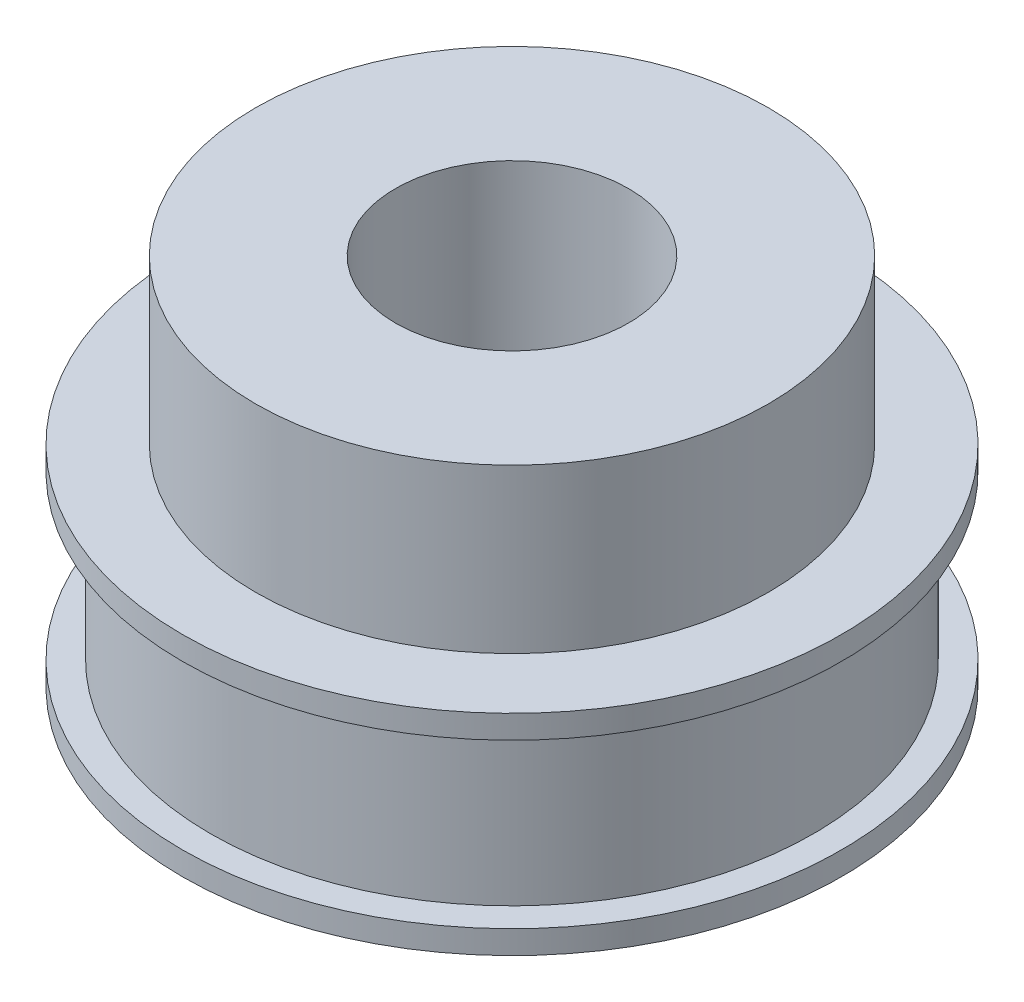
SolidWorks part; units mm, degrees
ref_plane "前视基准面" through (0, 0, 0) normal (0, 0, 1) x (1, 0, 0)
ref_plane "上视基准面" through (0, 0, 0) normal (0, 1, 0) x (1, 0, 0)
ref_plane "右视基准面" through (0, 0, 0) normal (1, 0, 0) x (0, 0, -1)
sketch "草图1" plane through (0, 0, 0) normal (0, 1, 0) x (1, 0, 0)
  circle A0 centre (0, 0) radius 12.935
  dimension "D1" = 25.87
extrude "凸台-拉伸1" add sketch "草图1" along normal blind 7
ref_plane "基准面1" through (0, 3.5, 0) normal (0, 1, 0) x (1, 0, 0)
sketch "草图2" plane through (0, 7, 0) normal (0, 1, 0) x (1, 0, 0)
  circle A0 centre (0, 0) radius 14.135
  circle A1 centre (0, 0) radius 12.935
  circle A2 centre (0, 0) radius 12.935 construction
  dimension "D2" = 1.2
  dimension "D1" = 0
extrude "凸台-拉伸2" add sketch "草图2" along normal blind 1
mirror "镜向1" about plane through (0, 3.5, 0) normal (0, 1, 0) of "凸台-拉伸2"
sketch "草图3" plane through (0, 8, 0) normal (0, 1, 0) x (1, 0, 0)
  circle A0 centre (0, 0) radius 11
  dimension "D1" = 22
extrude "凸台-拉伸3" add sketch "草图3" along normal offset from surface (7 mm away) 16 up to face at (0, -1, 14.135)
sketch "草图4" plane through (0, 15, 0) normal (0, 1, 0) x (1, 0, 0)
  circle A0 centre (0, 0) radius 5
  dimension "D1" = 10
extrude "切除-拉伸1" cut sketch "草图4" against normal through all
